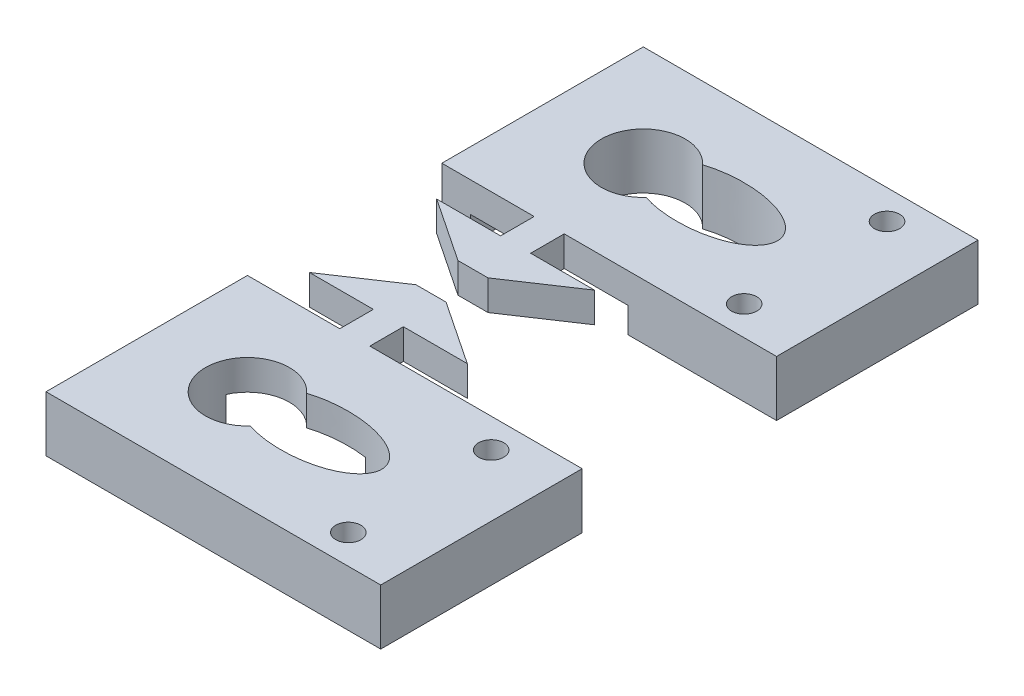
SolidWorks part; units mm, degrees
ref_plane "Front" through (0, 0, 0) normal (0, 0, 1) x (1, 0, 0)
ref_plane "Top" through (0, 0, 0) normal (0, 1, 0) x (1, 0, 0)
ref_plane "Right" through (0, 0, 0) normal (1, 0, 0) x (0, 0, -1)
sketch "Sketch1" plane through (0, 0, 0) normal (0, 1, 0) x (1, 0, 0)
  line L0 (-1.7907, 2) -> (-9.398, 2)
  line L2 (-1.7907, -2) -> (-1.7907, 2)
  line L4 (1.7907, -2) -> (1.7907, 2)
  line L7 (-9.398, 2) -> (-1.7907, 7.08)
  line L8 (-1.7907, 7.08) -> (1.7907, 7.08)
  line L9 (1.7907, 7.08) -> (9.398, 2)
  line L10 (9.398, 2) -> (1.7907, 2)
  line L11 (1.7907, -2) -> (27.088, -2)
  line L12 (-1.7907, -2) -> (-12.79, -2)
  line L13 (-12.79, -2) -> (-12.79, -26)
  line L14 (-12.79, -26) -> (27.088, -26)
  line L15 (27.088, -26) -> (27.088, -2)
  line L16 (27.088, -2) -> (1.7907, -2)
  point P0 (0, 0)
  point P17 (0, 7.08)
  point P24 (1.7907, 0)
  dimension "D1" = 18.796
  dimension "D2" = 3.5814
  dimension "D3" = 39.878
  dimension "D4" = 24
  dimension "D5" = 5.08
  dimension "D6" = 12.79
  dimension "D7" = 4
extrude "Boss-Extrude1" add sketch "Sketch1" along normal blind 3.5814 contours L14 L15 L11 L4 L10 L9 L8 L7 L0 L2 L12 L13 region at (6.6542, 0, 12.8119)
ref_plane "Plane1" through (0, 1.7907, 0) normal (0, 1, 0) x (1, 0, 0)
sketch "Sketch7" plane through (0, 0, 0) normal (0, 1, 0) x (1, 0, 0)
  line L1 (-12.79, -2) -> (27.088, -2)
  line L2 (-12.79, -2) -> (-12.79, -26)
  line L3 (-12.79, -26) -> (27.088, -26)
  line L4 (27.088, -2) -> (27.088, -26)
extrude "Boss-Extrude2" add sketch "Sketch7" along normal blind 3.035 and the other way blind 3.035
sketch "Sketch5" plane through (0, 3.5814, 0) normal (0, 1, 0) x (1, 0, 0)
  line L0 (-12.79, -2) -> (-12.79, -26) construction
  line L1 (-12.79, -14) -> (27.088, -14) construction
  line L2 (27.088, -26) -> (27.088, -2) construction
  circle A0 centre (-0.79, -14) radius 5
  circle A1 centre (19.738, -22.509) radius 1.5
  circle A2 centre (19.738, -5.491) radius 1.5
  ellipse E0 centre (7.21, -14) end of major axis (-0.79, -14) minor radius 4
  point P5 (-12.79, -14)
  dimension "D2" = 10
  dimension "D6" = 3
  dimension "D1" = 12
  dimension "D3" = 8
  dimension "D4" = 16
  dimension "D5" = 17.018
  dimension "D7" = 7.35
extrude "Cut-Extrude3" cut sketch "Sketch5" against normal through all both and the other way through all contours A0 L1 E0 | E0 L1 A0 | A0 L1 E0 | L1 A0 E0 | L1 E0 A0 | L1 A0 E0 | A1 | A2 region at (1.9147, 3.5814, 12.6918) region at (-1.952, 3.5814, 16.4717) region at (1.9147, 3.5814, 15.3082) region at (-1.952, 3.5814, 11.5283) region at (8.8346, 3.5814, 12.1829) region at (8.8346, 3.5814, 15.8171) region at (19.738, 3.5814, 22.509)
ref_plane "Plane2" through (0, 0, -17.08) normal (0, 0, -1) x (-1, 0, 0)
sketch "Sketch8" plane through (0, 0, 2) normal (0, 0, -1) x (-1, 0, 0)
  line L0 (-27.088, -3.035) -> (12.79, -3.035) construction
  line L1 (-9.398, 0) -> (9.398, 0)
  line L2 (-9.398, 0) -> (-9.398, -3.035)
  line L3 (-9.398, -3.035) -> (9.398, -3.035)
  line L4 (9.398, 0) -> (9.398, -3.035)
  line L5 (-9.398, 3.5814) -> (-9.398, 0) construction
  line L6 (9.398, 3.5814) -> (9.398, 0) construction
  line L7 (-1.7907, 0) -> (1.7907, 0) construction
extrude "Cut-Extrude4" cut sketch "Sketch8" against normal blind 10
ref_plane "Plane3" through (0, 0, -9.58) normal (0, 0, -1) x (-1, 0, 0)
mirror "Mirror2" about plane through (0, 0, -9.58) normal (0, 0, -1) of bodies 108
sketch "Sketch9" plane through (0, -3.035, 0) normal (0, -1, 0) x (-1, 0, 0)
  line L0 (-24.088, 38.16) -> (-24.088, 28.16) construction
  line L1 (-27.088, 45.16) -> (-27.088, 21.16) construction
  text T0 "Lt."
  point P3 (-24.088, 33.16)
  point P6 (-27.088, 33.16)
  dimension "D1" = 10
  dimension "D2" = 3
extrude "Cut-Extrude5" cut sketch "Sketch9" against normal blind 2
sketch "Sketch10" plane through (0, -3.035, 0) normal (0, -1, 0) x (1, 0, 0)
  line L0 (24.088, 19.5) -> (24.088, 8.5) construction
  line L1 (27.088, 26) -> (27.088, 2) construction
  text T0 "Rt."
  point P4 (27.088, 14)
  point P5 (24.088, 14)
  dimension "D1" = 11
  dimension "D2" = 3
extrude "Cut-Extrude6" cut sketch "Sketch10" against normal blind 2
